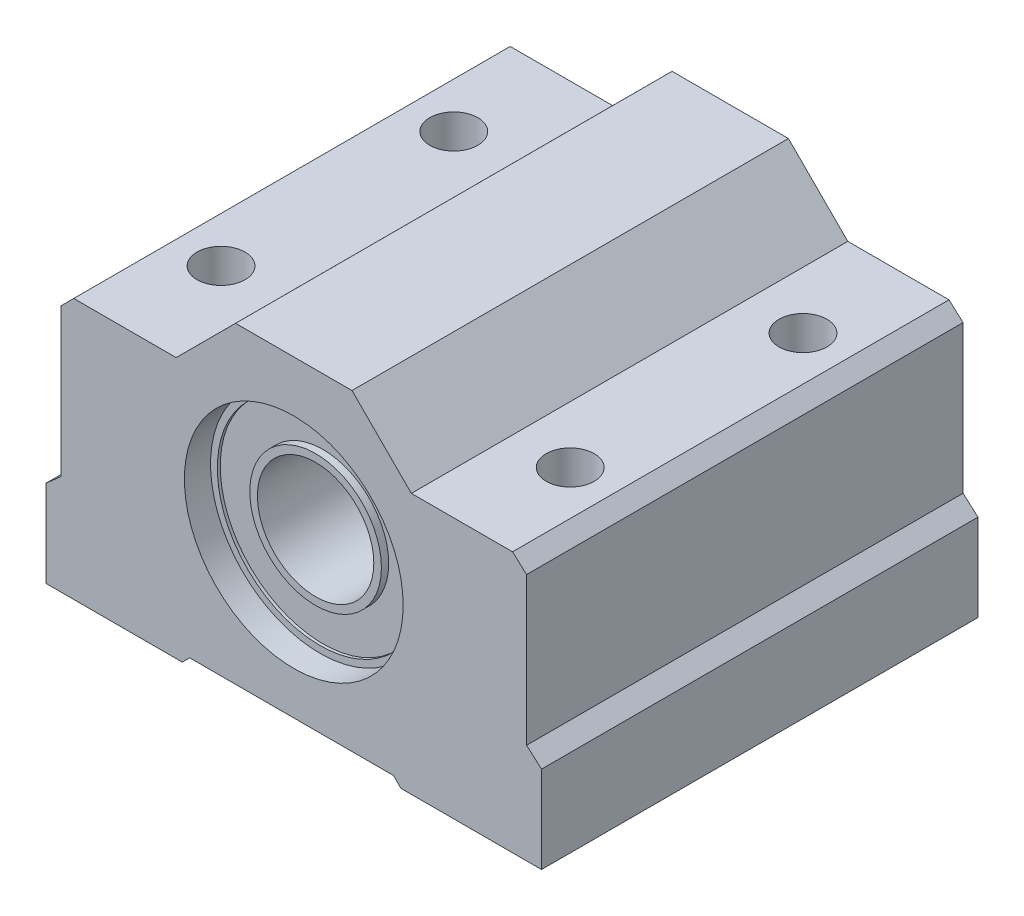
SolidWorks part; units mm, degrees
ref_plane "Plan de face" through (0, 0, 0) normal (0, 0, 1) x (1, 0, 0)
ref_plane "Plan de dessus" through (0, 0, 0) normal (0, 1, 0) x (1, 0, 0)
ref_plane "Plan de droite" through (0, 0, 0) normal (1, 0, 0) x (0, 0, -1)
sketch "Esquisse1" plane through (0, 0, 0) normal (0, 0, 1) x (1, 0, 0)
  line L0 (37.9997, 220.8672) -> (334.6664, 220.8672) construction
  line L1 (-17.03, -10.9738) -> (-7.6627, -10.9738)
  line L2 (-7.6627, -10.9738) -> (-7.1532, -10.4644)
  line L3 (-7.1532, -10.4644) -> (6.8576, -10.4644)
  line L4 (6.8576, -10.4644) -> (7.3671, -10.9738)
  line L5 (7.3671, -10.9738) -> (17.03, -10.9738)
  line L6 (17.03, -10.9738) -> (17.03, -4.9953)
  line L7 (17.03, -4.9953) -> (16.0028, -4.0892)
  line L8 (16.0028, -4.0892) -> (16.0028, 6.0714)
  line L9 (16.0028, 6.0714) -> (15.0375, 6.9443)
  line L10 (15.0375, 6.9443) -> (8.0819, 6.9443)
  line L11 (8.0819, 6.9443) -> (4, 11.0262)
  line L12 (4, 11.0262) -> (-4, 11.0262)
  line L13 (-4, 11.0262) -> (-8.0839, 6.9443)
  line L14 (-8.0839, 6.9443) -> (-15.1244, 6.9443)
  line L15 (-15.1244, 6.9443) -> (-15.9972, 6.0714)
  line L16 (-15.9972, 6.0714) -> (-15.9972, -4.0892)
  line L17 (-15.9972, -4.0892) -> (-17.03, -5.0045)
  line L18 (-17.03, -5.0045) -> (-17.03, -10.9738)
  circle A0 centre (0, 0) radius 4
  circle A1 centre (0, 0) radius 4.5234
  circle A2 centre (0, 0) radius 7.0518
  circle A3 centre (0, 0) radius 7.519
  dimension "D1" = 8
  dimension "D2" = 22
  dimension "D3" = 34.06
  dimension "D4" = 17.03
  dimension "D5" = 32
  dimension "D6" = 8
  dimension "D7" = 4
extrude "Boss.-Extru.1" add sketch "Esquisse1" against normal blind 30 contours L17 L18 L1 L2 L3 L4 L5 L6 L7 L8 L9 L10 L11 L12 L13 L14 L15 L16 A3 region at (-16.6245, -7.9891, 0)
extrude "Boss.-Extru.2" add sketch "Esquisse1<3>" against normal blind 28 separate body contours A2 A1 region at (-6.8523, 0, 0)
sketch "Esquisse1<3>" plane through (0, 0, 0) normal (0, 0, 1) x (1, 0, 0) same geometry as "Esquisse1"
extrude "Boss.-Extru.3" add sketch "Esquisse1<4>" against normal blind 30 contours A3 A2 region at (-7.3063, 0, 0)
sketch "Esquisse1<4>" plane through (0, 0, 0) normal (0, 0, 1) x (1, 0, 0) same geometry as "Esquisse1"
extrude "Boss.-Extru.4" add sketch "Esquisse1<5>" against normal blind 28.5 contours A1 A0 region at (-4.3955, 0, 0)
sketch "Esquisse1<5>" plane through (0, 0, 0) normal (0, 0, 1) x (1, 0, 0) same geometry as "Esquisse1"
extrude "Enlèv. mat.-Extru.1" cut sketch "Esquisse1<6>" against normal blind 1.5 contours A1 A0 region at (-4.3955, 0, 0)
sketch "Esquisse1<6>" plane through (0, 0, 0) normal (0, 0, 1) x (1, 0, 0) same geometry as "Esquisse1"
extrude "Enlèv. mat.-Extru.2" cut sketch "Esquisse1<7>" against normal blind 2 contours A2 A1 region at (-6.8523, 0, 0)
sketch "Esquisse1<7>" plane through (0, 0, 0) normal (0, 0, 1) x (1, 0, 0) same geometry as "Esquisse1"
extrude "Enlèv. mat.-Extru.3" cut sketch "Esquisse1<8>" against normal blind 1.8 contours A3 A2 region at (-7.3063, 0, 0)
sketch "Esquisse1<8>" plane through (0, 0, 0) normal (0, 0, 1) x (1, 0, 0) same geometry as "Esquisse1"
extrude "Enlèv. mat.-Extru.4" cut sketch "Esquisse1<9>" along normal blind 1.8 from surface contours A3 A2 region at (-7.3063, 0, 0) starting at face at (-0.0372, -1.1683, -30)
sketch "Esquisse1<9>" plane through (0, 0, 0) normal (0, 0, 1) x (1, 0, 0) same geometry as "Esquisse1"
sketch "Esquisse2" plane through (0, -10.9738, 0) normal (0, -1, 0) x (1, 0, 0)
  line L0 (74.1667, 293.5) -> (370.8333, 293.5) construction
  line L1 (7.3671, 0) -> (17.03, 0) construction
  line L2 (-17.03, -30) -> (-17.03, 0) construction
  circle A0 centre (-12, -7) radius 1.65
  circle A1 centre (12, -7) radius 1.65
  circle A2 centre (12, -23) radius 1.65
  circle A3 centre (-12, -23) radius 1.65
  dimension "D1" = 3.3
  dimension "D2" = 3.3
  dimension "D3" = 3.3
  dimension "D4" = 3.3
  dimension "D10" = 16
  dimension "D5" = 0
  dimension "D6" = 0
  dimension "D7" = 0
  dimension "D8" = 0
  dimension "D9" = 24
  dimension "D11" = 7
  dimension "D12" = 5.03
hole_wizard "M4x0.7 Tapped Hole1" positions "Sketch4" profile "Sketch3" tap size "M4x0.7" standard "ANSI Metric" end condition through all
sketch "Sketch4" plane through (0, -10.9738, 0) normal (0, -1, 0) x (-1, 0, 0)
  point P0 (-12, 7)
  point P3 (-12, 23)
  point P6 (12, 23)
  point P9 (12, 7)
sketch "Sketch3" plane through (12, -10.9738, -7) normal (1, 0, 0) x (0, 0, -1)
  line L0 (0, 0) -> (0, 22)
  line L1 (0, 22) -> (1.65, 22)
  line L2 (1.65, 22) -> (1.65, 0)
  line L5 (1.65, 0) -> (0, 0)
  line L11 (0, -6.35) -> (0, 107.95) construction
  dimension "Thru Tap Drill Dia." = 3.3
  dimension "Thru Tap Drill Depth" = 22
cosmetic thread "Hole Thread1" parameters "D2"=4
cosmetic thread "Hole Thread2" parameters "D2"=4
cosmetic thread "Hole Thread3" parameters "D2"=4
cosmetic thread "Hole Thread4" parameters "D2"=4
